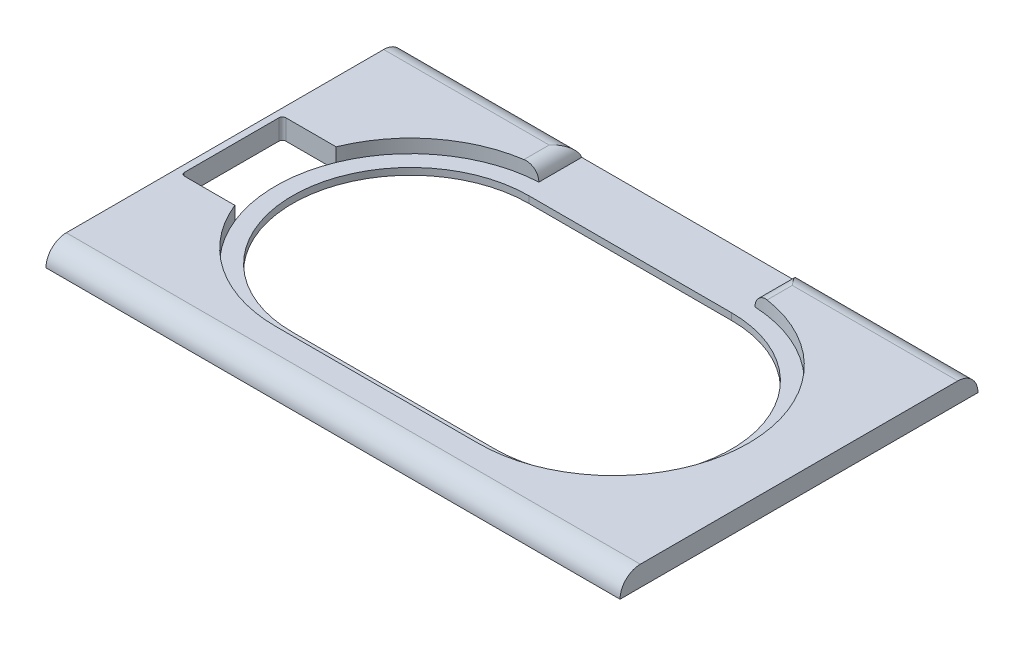
SolidWorks part; units mm, degrees
ref_plane "Front Plane" through (0, 0, 0) normal (0, 0, 1) x (1, 0, 0)
ref_plane "Top Plane" through (0, 0, 0) normal (0, 1, 0) x (1, 0, 0)
ref_plane "Right Plane" through (0, 0, 0) normal (1, 0, 0) x (0, 0, -1)
sketch "Sketch1" plane through (0, 0, 0) normal (0, 1, 0) x (1, 0, 0)
  line L0 (0, 0) -> (170, 0)
  line L1 (0, 0) -> (0, -106)
  line L2 (0, -106) -> (170, -106)
  line L3 (170, -106) -> (170, 0)
  dimension "D1" = 170
  dimension "D2" = 106
extrude "Boss-Extrude1" add sketch "Sketch1" along normal blind 6
fillet "Fillet1" radius 6 2 edges at (85, 6, 106) (85, 6, 0)
sketch "Sketch2" plane through (0, 6, 0) normal (0, 1, 0) x (1, 0, 0)
  line L0 (0, -53) -> (170, -53) construction
  line L1 (0, -6) -> (0, -100) construction
  line L2 (170, -100) -> (170, -6) construction
  line L3 (85, -53) -> (115, -53) construction
  line L4 (115, -53) -> (155, -53) construction
  line L5 (85, -53) -> (55, -53) construction
  line L6 (55, -53) -> (15, -53) construction
  line L7 (55, -13) -> (115, -13)
  line L8 (115, -93) -> (55, -93)
  arc A0 (55, -13) -> (55, -93) centre (55, -53) ccw
  arc A1 (115, -93) -> (115, -13) centre (115, -53) ccw
  dimension "D1" = 30
  dimension "D2" = 40
extrude "Cut-Extrude1" cut sketch "Sketch2" against normal blind 4
sketch "Sketch3" plane through (0, 6, 0) normal (0, 1, 0) x (1, 0, 0)
  line L0 (15, -53) -> (0, -53) construction
  line L1 (0, -53) -> (2, -53) construction
  line L2 (2, -53) -> (2, -38)
  line L3 (2, -38) -> (17.919, -38)
  line L4 (2, -53) -> (2, -68)
  line L5 (2, -68) -> (17.919, -68)
  arc A0 (55, -13) -> (55, -93) centre (55, -53) ccw construction
  arc A1 (17.919, -38) -> (17.919, -68) centre (55, -53) ccw
  dimension "D1" = 15
  dimension "D2" = 15
  dimension "D3" = 15
extrude "Cut-Extrude2" cut sketch "Sketch3" against normal through all
sketch "Sketch5" plane through (0, 0, 0) normal (0, 0, 1) x (1, 0, 0)
  line L0 (85, 11.4101) -> (85, -6.317) construction
  line L1 (170, 6) -> (0, 6) construction
  line L2 (49, 6) -> (121, 6)
  line L3 (170, 0) -> (0, 0) construction
  line L5 (53, 2) -> (117, 2)
  arc A0 (53, 2) -> (49, 6) centre (49, 2) ccw
  arc A1 (117, 2) -> (121, 6) centre (121, 2) cw
  point P0 (85, 2)
  point P10 (85, 6)
  point P14 (85, 0)
  point P16 (85, 6)
extrude "Cut-Extrude3" cut sketch "Sketch5" along normal blind 25
sketch "Sketch8" plane through (0, 2, 0) normal (0, 1, 0) x (1, 0, 0)
  line L0 (85, -0.3431) -> (85, -18) construction
  line L1 (53, -0.3431) -> (117, -0.3431) construction
  line L2 (55, -93) -> (115, -93) construction
  line L3 (55, -18) -> (115, -18)
  line L4 (55, -88) -> (115, -88)
  line L5 (85, -88) -> (85, -93) construction
  arc A0 (55, -18) -> (55, -88) centre (55, -53) ccw
  arc A1 (115, -18) -> (115, -88) centre (115, -53) cw
extrude "Cut-Extrude4" cut sketch "Sketch8" against normal through all
sketch "Sketch9" plane through (0, 6, 0) normal (0, 1, 0) x (1, 0, 0)
fillet "Fillet2" radius 1 2 edges at (2, 3, 38) (2, 3, 68)
